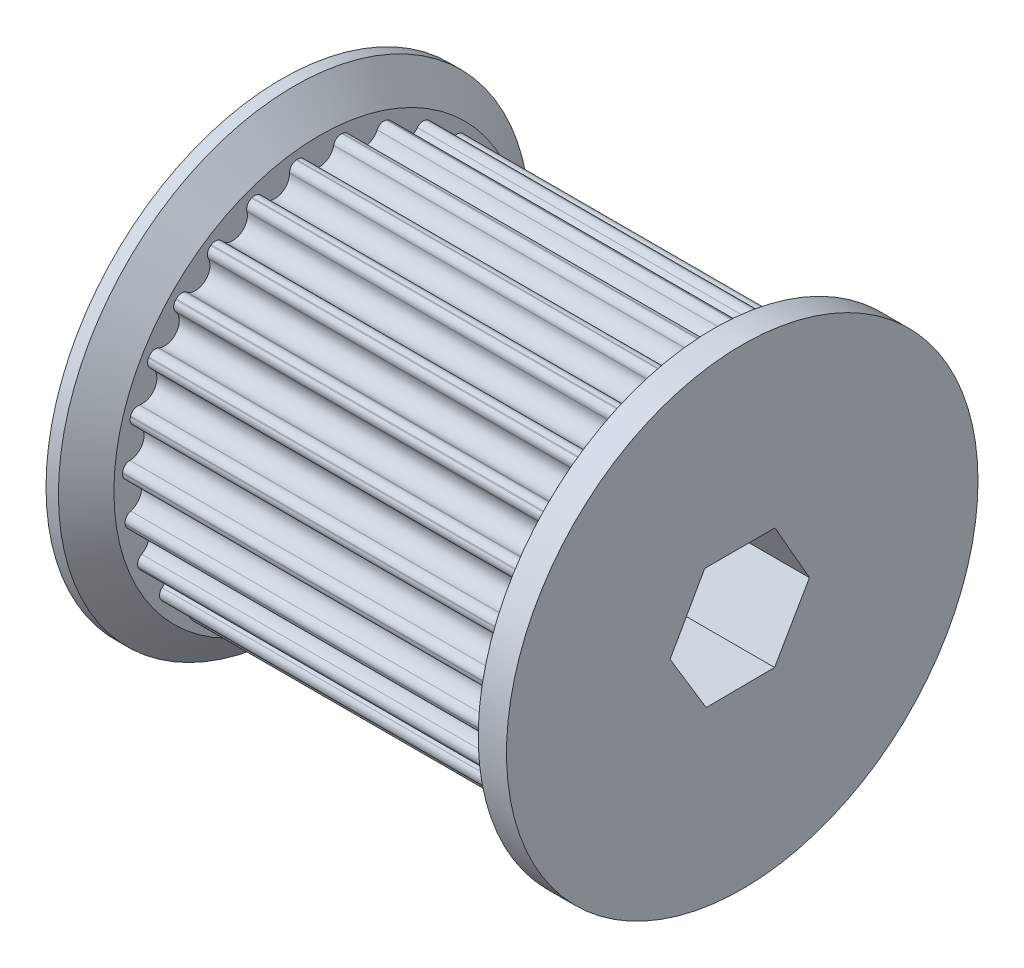
SolidWorks part; units mm, degrees
ref_plane "Front Plane" through (0, 0, 0) normal (0, 0, 1) x (1, 0, 0)
ref_plane "Top Plane" through (0, 0, 0) normal (0, 1, 0) x (1, 0, 0)
ref_plane "Right Plane" through (0, 0, 0) normal (1, 0, 0) x (0, 0, -1)
sketch "Sketch1" plane through (0, 0, 0) normal (1, 0, 0) x (0, 0, -1)
  circle A0 centre (0, 0) radius 20.915
  dimension "D1" = 41.83
extrude "Boss-Extrude1" add sketch "Sketch1" along normal blind 41.8338 contours A0
sketch "Sketch8" plane through (41.8338, 0, 0) normal (1, 0, 0) x (0, 0, -1)
  line L1 (0, 0) -> (0, 50.3807) construction
  line L7 (-2.5, 21.3391) -> (0, 0) construction
  line L8 (0, 0) -> (2.5, 21.3391) construction
  circle A0 centre (0, 0) radius 21.485 construction
  circle A2 centre (0, 0) radius 20.915 construction
  arc A3 (-1.4883, 20.862) -> (1.4883, 20.862) centre (0, 20.4573) ccw
  arc A6 (-1.4883, 20.862) -> (1.4883, 20.862) centre (0, 0) cw
  point P4 (0, 0.1768)
  point P15 (0, 18.915)
  point P16 (0, 20.915)
  dimension "D4" = 1.5423
  dimension "D2" = 42.97
  dimension "D1" = 5
  dimension "D3" = 2.5
  dimension "D5" = 2
sketch "Sketch9" plane through (0, 0, 0) normal (-1, 0, 0) x (0, 0, 1)
  line L0 (-3.4711, 6.4445) -> (-7.1255, 0.0437)
  line L1 (-7.1255, 0.0437) -> (-3.4298, -6.3571)
  line L2 (-3.4298, -6.3571) -> (3.8268, -6.4097)
  line L3 (3.8268, -6.4097) -> (7.6559, -0.0635)
  line L4 (7.6559, -0.0635) -> (3.9818, 6.4445)
  line L5 (3.9818, 6.4445) -> (-3.4711, 6.4445)
extrude "Cut-Extrude6" cut sketch "Sketch8" against normal blind 43 contours A6 A3
fillet "Fillet4" radius 0.8 2 edges at (20.9169, 20.862, -1.4883) (20.9169, 20.862, 1.4883)
sketch "Sketch10" plane through (41.8338, 0, 0) normal (1, 0, 0) x (0, 0, -1)
  circle A0 centre (0, 0) radius 25
  dimension "D1" = 50
sketch "Sketch11" plane through (0, 0, 0) normal (-1, 0, 0) x (0, 0, 1)
  circle A0 centre (0, 0) radius 25
  dimension "D1" = 50
pattern_circular "CirPattern1" count 27 over 360 about axis through (41.8338, 0, 0) along (-1, 0, 0) of "Cut-Extrude6", "Fillet4"
extrude "Boss-Extrude7" add sketch "Sketch10" along normal blind 3
extrude "Boss-Extrude8" add sketch "Sketch11" along normal blind 4
chamfer "Chamfer1" distance 3.2 angle 40 1 edges at (0, 0, 25) first distance on face at (0, 0, 0)
extrude "Cut-Extrude5" cut sketch "Sketch9" against normal through all both and the other way through all
